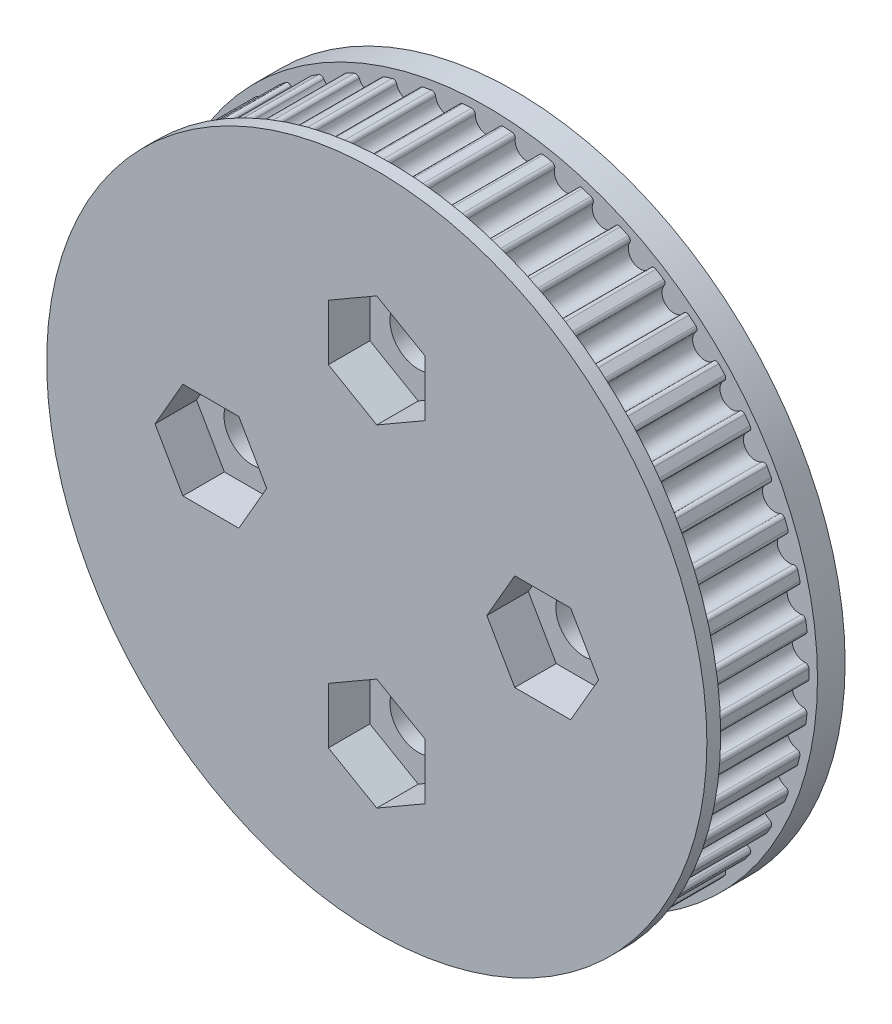
SolidWorks part; units mm, degrees
ref_plane "Front Plane" through (0, 0, 0) normal (1, 0, 0) x (0, 1, 0)
ref_plane "Top Plane" through (0, 0, 0) normal (0, 0, 1) x (0, 1, 0)
ref_plane "Right Plane" through (0, 0, 0) normal (0, 1, 0) x (-1, 0, 0)
sketch "Sketch1" plane through (0, 0, 0) normal (0, 0, 1) x (0, 1, 0)
  line L0 (0, 0) -> (0, 23.2582)
  line L1 (0, 0) -> (1.4416, 22.9129) construction
  line L2 (0, 0) -> (2.915, 23.0748)
  arc A2 (0.6393, 23.2495) -> (2.2797, 23.1462) centre (1.4416, 22.9129) ccw
  arc A3 (0, 23.2582) -> (0.6393, 23.2495) centre (0, 0) cw
  arc A4 (2.2797, 23.1462) -> (2.915, 23.0748) centre (0, 0) cw
  dimension "D4" = 1.74
  dimension "D3" = 22.9582
  dimension "D1" = 23.2582
  dimension "D2" = 7.2
  dimension "D5" = 23.2582
extrude "Boss-Extrude2" add sketch "Sketch1" along normal blind 3.5 and the other way blind 3.5 contours L1 L2 A4 A2 | L0 L1 A2 A3 region at (-15.1166, 0.4578, 0) region at (-15.0548, 1.4404, 0)
fillet "Fillet2" radius 0.26 2 edges at (-23.1462, 2.2797, 0) (-23.2495, 0.6393, 0)
pattern_circular "CirPattern6" count 50 over 360 about axis through (0, 0, -3.5) along (0, 0, 1) of "Fillet2", "Boss-Extrude2"
sketch "Sketch2" plane through (0, 0, 3.5) normal (0, 0, 1) x (1, 0, 0)
  line L0 (9.9793, -3.5) -> (14.0207, -3.5)
  line L1 (0, 16.0415) -> (-3.5, 14.0207)
  line L2 (-3.5, 14.0207) -> (-3.5, 9.9793)
  line L3 (-3.5, 9.9793) -> (0, 7.9585)
  line L4 (0, 7.9585) -> (3.5, 9.9793)
  line L5 (3.5, 9.9793) -> (3.5, 14.0207)
  line L6 (3.5, 14.0207) -> (0, 16.0415)
  line L7 (7.9585, 0) -> (9.9793, -3.5)
  line L8 (9.9793, 3.5) -> (7.9585, 0)
  line L9 (14.0207, 3.5) -> (9.9793, 3.5)
  line L10 (16.0415, 0) -> (14.0207, 3.5)
  line L11 (14.0207, -3.5) -> (16.0415, 0)
  line L12 (-3.5, -9.9793) -> (-3.5, -14.0207)
  line L13 (0, -7.9585) -> (-3.5, -9.9793)
  line L14 (3.5, -9.9793) -> (0, -7.9585)
  line L15 (3.5, -14.0207) -> (3.5, -9.9793)
  line L16 (0, -16.0415) -> (3.5, -14.0207)
  line L17 (-3.5, -14.0207) -> (0, -16.0415)
  line L18 (-9.9793, 3.5) -> (-14.0207, 3.5)
  line L19 (-7.9585, 0) -> (-9.9793, 3.5)
  line L20 (-9.9793, -3.5) -> (-7.9585, 0)
  line L21 (-14.0207, -3.5) -> (-9.9793, -3.5)
  line L22 (-16.0415, 0) -> (-14.0207, -3.5)
  line L23 (-14.0207, 3.5) -> (-16.0415, 0)
  circle A0 centre (0, 0) radius 23.875
  circle A1 centre (0, 0) radius 12 construction
  circle A2 centre (0, 12) radius 2.05
  circle A3 centre (0, 12) radius 3.5 construction
  circle A4 centre (12, 0) radius 2.05
  circle A5 centre (0, -12) radius 2.05
  circle A6 centre (-12, 0) radius 2.05
  dimension "D1" = 24
  dimension "D2" = 4.1
  dimension "D3" = 4
extrude "Boss-Extrude3" add sketch "Sketch2" along normal blind 1 contours A0 L6 L5 L4 L3 L2 L1 L11 L0 L7 L8 L9 L10 L17 L12 L13 L14 L15 L16 L23 L18 L19 L20 L21 L22 region at (0, 0, 3.5)
extrude "Cut-Extrude4" cut sketch "Sketch2<6>" against normal blind 2 contours L12 L17 L16 L15 L14 L13 A5 | L0 L11 L10 L9 L8 L7 A4 | L18 L23 L22 L21 L20 L19 A6 | L5 L6 L1 L2 L3 L4 A2 region at (9.0615, -1.6965, 3.5) region at (1.6965, 14.9385, 3.5) region at (-1.6965, -9.0615, 3.5) region at (-9.0615, 1.6965, 3.5)
sketch "Sketch2<6>" plane through (0, 0, 3.5) normal (0, 0, 1) x (1, 0, 0) same geometry as "Sketch2"
extrude "Cut-Extrude5" cut sketch "Sketch2<7>" against normal blind 7 contours A4 | A5 | A6 | A2 region at (0, 12, 3.5) region at (12, 0, 3.5) region at (0, -12, 3.5) region at (-12, 0, 3.5)
sketch "Sketch2<7>" plane through (0, 0, 3.5) normal (0, 0, 1) x (1, 0, 0) same geometry as "Sketch2"
extrude "Boss-Extrude4" add sketch "Sketch2<8>" against normal blind 2 from surface contours A0 L6 L5 L4 L3 L2 L1 L11 L0 L7 L8 L9 L10 L17 L12 L13 L14 L15 L16 L23 L18 L19 L20 L21 L22 | L5 L6 L1 L2 L3 L4 A2 | L0 L11 L10 L9 L8 L7 A4 | L12 L17 L16 L15 L14 L13 A5 | L18 L23 L22 L21 L20 L19 A6 region at (9.0615, -1.6965, 3.5) region at (1.6965, 14.9385, 3.5) region at (-1.6965, -9.0615, 3.5) region at (-9.0615, 1.6965, 3.5) region at (0, 0, 3.5) starting at face at (14.05, 0, -3.5)
sketch "Sketch2<8>" plane through (0, 0, 3.5) normal (0, 0, 1) x (1, 0, 0) same geometry as "Sketch2"
sketch "Sketch5" plane through (0, 0, -5.5) normal (0, 0, -1) x (1, 0, 0)
  circle A0 centre (0, 0) radius 16.25
  dimension "D1" = 32.5
extrude "Cut-Extrude6" cut sketch "Sketch5" against normal blind 3
equation "\"D3@Sketch1\"=\"PitchDiameter\" / 2 - 1.17 - 0.615 + 1.74/2"
equation "\"Teeth\"= 50"
equation "\"Pitch\"= 3mm"
equation "\"PitchDiameter\"= \"Pitch\" * \"Teeth\" / PI"
equation "\"D1@Sketch1\"=\"PitchDiameter\"/2 - 0.615"
equation "\"D2@Sketch1\"=360 / \"Teeth\""
equation "\"D5@Sketch1\"=\"PitchDiameter\"/2 - 0.615"
